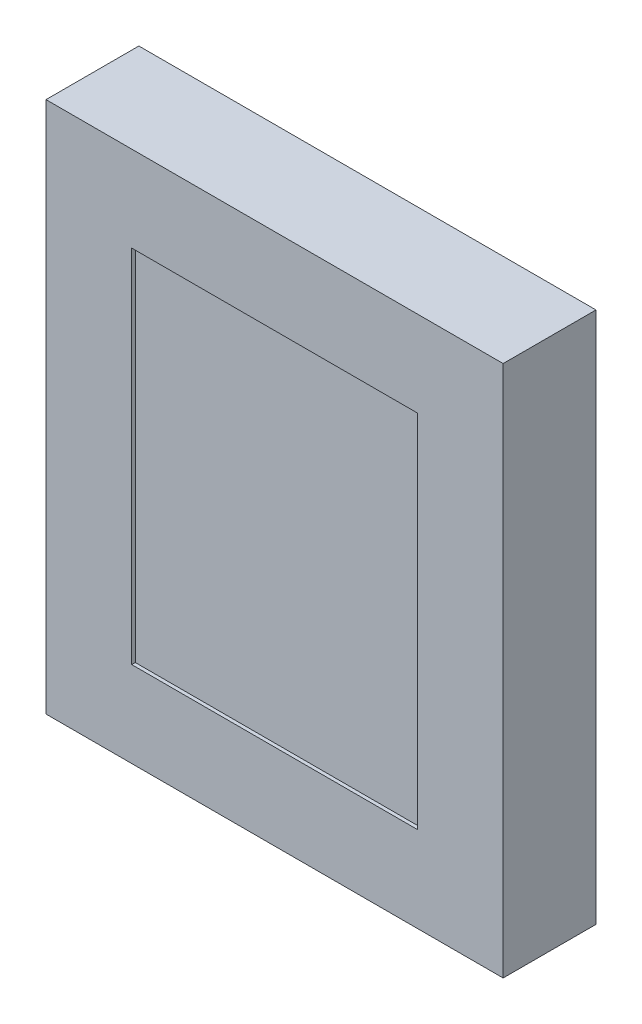
SolidWorks part; units mm, degrees
ref_plane "Plano frontal" through (0, 0, 0) normal (0, 0, 1) x (1, 0, 0)
ref_plane "Plano superior" through (0, 0, 0) normal (0, 1, 0) x (1, 0, 0)
ref_plane "Plano direito" through (0, 0, 0) normal (1, 0, 0) x (0, 0, -1)
sketch "Esboço1" plane through (0, 0, 0) normal (0, 0, 1) x (1, 0, 0)
  line L1 (200, 252.5) -> (-200, 252.5)
  line L2 (200, 252.5) -> (200, -252.5)
  line L3 (200, -252.5) -> (-200, -252.5)
  line L4 (-200, 252.5) -> (-200, -252.5)
  line L5 (200, 252.5) -> (-200, -252.5) construction
  line L6 (200, -252.5) -> (-200, 252.5) construction
  point P0 (0, 0)
  dimension "D1" = 505
  dimension "D2" = 400
extrude "Ressalto-extrusão1" add sketch "Esboço1" along normal blind 60 and the other way blind 60
sketch "Esboço2" plane through (0, 0, 0) normal (0, 0, 1) x (1, 0, 0)
  line L4 (-200, 252.5) -> (-200, -252.5)
  line L5 (-200, -252.5) -> (200, -252.5)
  line L6 (200, -252.5) -> (200, 252.5)
  line L7 (200, 252.5) -> (-200, 252.5)
  line L8 (-200, 252.5) -> (-200, -252.5)
  line L9 (-200, -252.5) -> (200, -252.5)
  line L10 (200, -252.5) -> (200, 252.5)
  line L11 (200, 252.5) -> (-200, 252.5)
  line L16 (-320, 372.5) -> (-320, -372.5)
  line L17 (-320, -372.5) -> (320, -372.5)
  line L18 (320, -372.5) -> (320, 372.5)
  line L19 (320, 372.5) -> (-320, 372.5)
  line L20 (-320, 372.5) -> (-320, -372.5)
  line L21 (-320, -372.5) -> (320, -372.5)
  line L22 (320, -372.5) -> (320, 372.5)
  line L23 (320, 372.5) -> (-320, 372.5)
  dimension "D1" = 0
  dimension "D2" = 120
extrude "Ressalto-extrusão2" add sketch "Esboço2" along normal blind 65 and the other way blind 65 separate body
